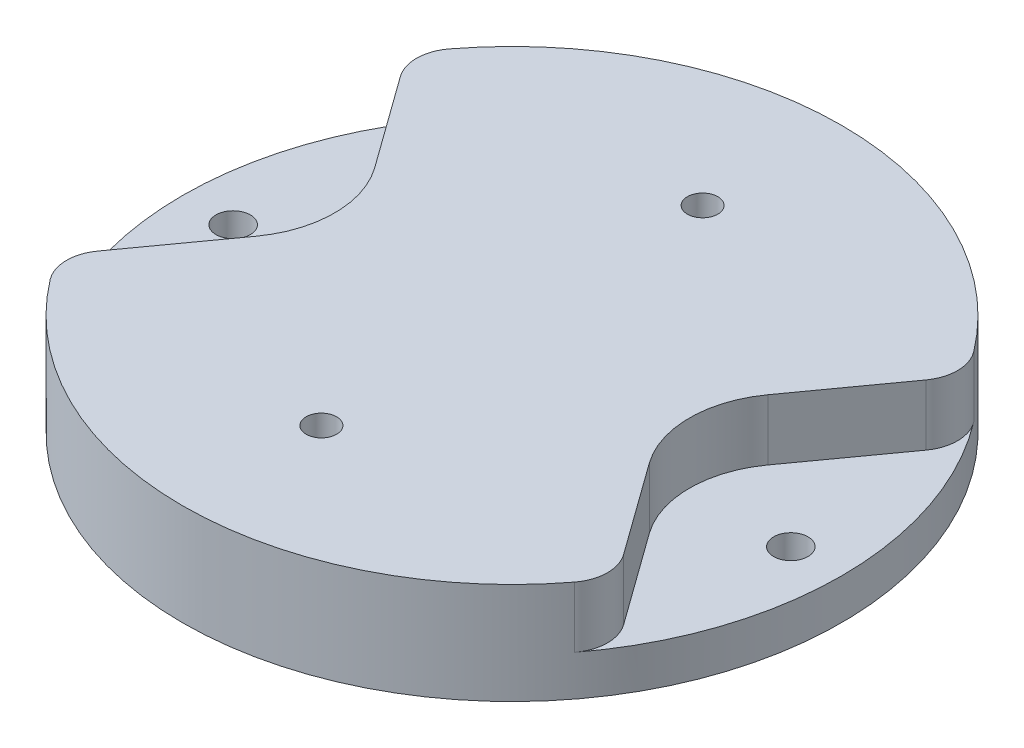
SolidWorks part; units mm, degrees
ref_plane "Front Plane" through (0, 0, 0) normal (0, 0, 1) x (1, 0, 0)
ref_plane "Top Plane" through (0, 0, 0) normal (0, 1, 0) x (1, 0, 0)
ref_plane "Right Plane" through (0, 0, 0) normal (1, 0, 0) x (0, 0, -1)
sketch "Sketch1" plane through (0, 0, 0) normal (0, 1, 0) x (1, 0, 0)
  line L0 (-34.925, 0) -> (34.925, 0) construction
  line L1 (0, 23.876) -> (0, -23.876) construction
  line L2 (-24.6219, 7.4253) -> (-35.0174, 21.8497)
  line L3 (-24.6219, -7.4253) -> (-35.0174, -21.8497)
  line L4 (24.6219, 7.4253) -> (35.0174, 21.8497)
  line L5 (24.6219, -7.4253) -> (35.0174, -21.8497)
  circle A0 centre (0, 0) radius 41.275
  circle A1 centre (-34.925, 0) radius 2.15
  circle A2 centre (34.925, 0) radius 2.15
  circle A3 centre (0, 23.876) radius 1.905
  circle A4 centre (0, -23.876) radius 1.905
  circle A5 centre (0, 23.876) radius 7.62
  circle A6 centre (0, -23.876) radius 7.62
  circle A7 centre (-34.925, 0) radius 12.7
  circle A8 centre (34.925, 0) radius 12.7
  point P19 (-37.3132, -17.6452)
  point P20 (-34.925, -21.9482)
  dimension "D1" = 82.55
  dimension "D2" = 4.3
  dimension "D4" = 47.752
  dimension "D5" = 3.81
  dimension "D6" = 25.4
  dimension "D7" = 15.24
  dimension "D3" = 69.85
  dimension "D8" = 17.78
extrude "Boss-Extrude1" add sketch "Sketch1" along normal blind 12.7 contours A0
extrude "Cut-Extrude2" cut sketch "Sketch1<4>" along normal through all contours A3 | A2 | A4 | A1
sketch "Sketch1<4>" plane through (0, 0, 0) normal (0, 1, 0) x (1, 0, 0) same geometry as "Sketch1"
extrude "Cut-Extrude3" cut sketch "Sketch1<5>" along normal blind 5.08 contours A6 A4 | A5 A3 | A5 | A6 region at (-7.4045, 0, -23.876) region at (-7.4045, 0, 23.876)
sketch "Sketch1<5>" plane through (0, 0, 0) normal (0, 1, 0) x (1, 0, 0) same geometry as "Sketch1"
extrude "Cut-Extrude4" cut sketch "Sketch1<6>" against normal blind 7.62 from surface contours A7 A0 L3 | A7 L2 A0 | A8 A0 L4 | A8 L5 A0 | A7 | A8 region at (-33.8712, 0, -15.2998) region at (33.8712, 0, -15.2998) region at (-33.8712, 0, 15.2998) region at (33.8712, 0, 15.2998) starting at face at (0, 12.7, -21.971)
sketch "Sketch1<6>" plane through (0, 0, 0) normal (0, 1, 0) x (1, 0, 0) same geometry as "Sketch1"
fillet "Fillet1" radius 5.08 4 edges at (35.0174, 8.89, 21.8497) (35.0174, 8.89, -21.8497) (-35.0174, 8.89, 21.8497) (-35.0174, 8.89, -21.8497)
